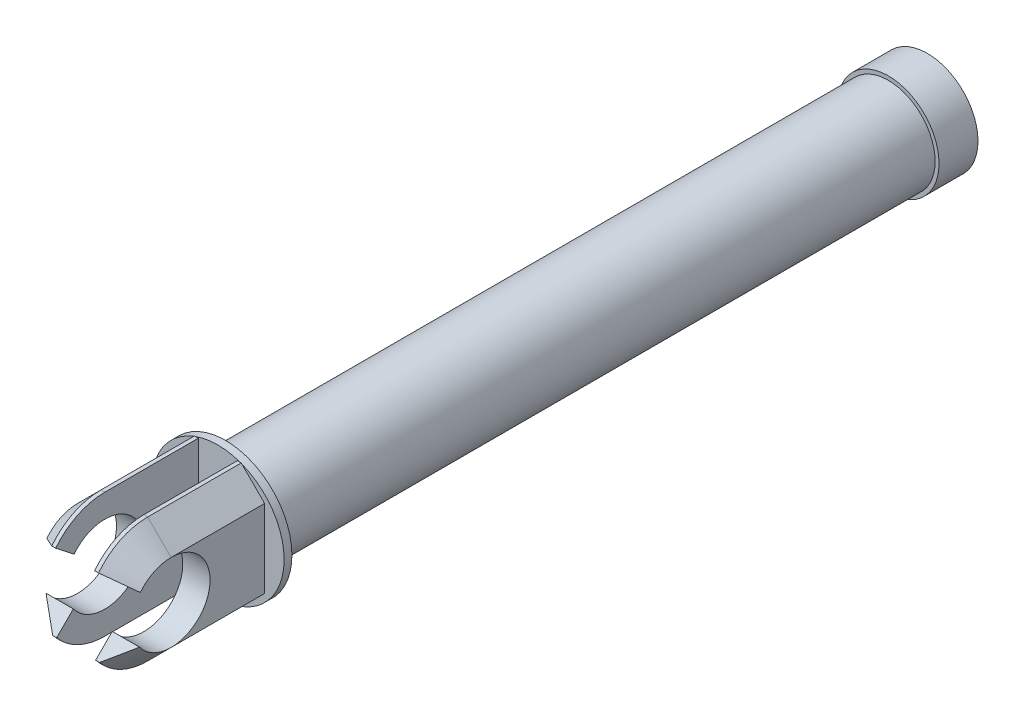
SolidWorks part; units mm, degrees
ref_plane "Front Plane" through (0, 0, 0) normal (0, 0, 1) x (1, 0, 0)
ref_plane "Top Plane" through (0, 0, 0) normal (0, 1, 0) x (1, 0, 0)
ref_plane "Right Plane" through (0, 0, 0) normal (1, 0, 0) x (0, 0, -1)
sketch "Sketch1" plane through (0, 0, 0) normal (0, 0, 1) x (1, 0, 0)
  circle A0 centre (0, 0) radius 12
  circle A1 centre (0, 0) radius 13
  dimension "D1" = 24
  dimension "D2" = 26
extrude "Boss-Extrude1" add sketch "Sketch1" along normal blind 10 contours A0 | A1 A0 | A0 | A1 region at (0, 0, 0) region at (-12.6323, 0, 0)
sketch "Sketch2" plane through (0, 0, 10) normal (0, 0, 1) x (1, 0, 0)
  circle A0 centre (0, 0) radius 12
  dimension "D1" = 24
extrude "Boss-Extrude2" add sketch "Sketch2" along normal blind 170
sketch "Sketch3" plane through (0, 0, 180) normal (0, 0, 1) x (1, 0, 0)
  circle A0 centre (0, 0) radius 17
  dimension "D1" = 34
extrude "Boss-Extrude3" add sketch "Sketch3" along normal blind 2
sketch "Sketch4" plane through (0, 0, 0) normal (1, 0, 0) x (0, 0, -1)
  line L0 (-182, 16) -> (-206, 16)
  line L1 (-182, 17) -> (-182, -17) construction
  line L2 (-206, -16) -> (-182, -16)
  line L3 (-182, -16) -> (-182, 16)
  arc A0 (-206, 16) -> (-206, -16) centre (-206, 0) ccw
  circle A1 centre (-206, 0) radius 10
  point P7 (-182, 0)
  dimension "D2" = 16
  dimension "D3" = 20
  dimension "D1" = 24
extrude "Boss-Extrude4" add sketch "Sketch4" along normal mid plane 24
chamfer "Chamfer1" distance 6 angle 45 6 edges at (-12, -16, 194) (-12, 0, 222) (-12, 16, 194) (12, -16, 194) (12, 0, 222) (12, 16, 194)
sketch "Sketch5" plane through (0, 0, 0) normal (0, 1, 0) x (1, 0, 0)
  line L0 (-5.7446, -182) -> (5.7446, -182) construction
  line L1 (-6, -222) -> (6, -222) construction
  line L2 (6, -206) -> (6, -182) construction
  line L3 (6, -222) -> (6, -206) construction
  line L4 (-6, -206) -> (-6, -222) construction
  line L5 (-6, -182) -> (-6, -206) construction
  line L6 (-5.7446, -182) -> (5.7446, -182)
  line L7 (-6, -222) -> (6, -222)
  line L8 (6, -206) -> (6, -182)
  line L9 (6, -222) -> (6, -206)
  line L10 (-6, -206) -> (-6, -222)
  line L11 (-6, -182) -> (-6, -206)
  line L13 (-5, -182) -> (5, -182)
  line L14 (-5, -182) -> (-5, -223)
  line L15 (-5, -223) -> (5, -223)
  line L16 (5, -182) -> (5, -223)
  dimension "D1" = 1
  dimension "D2" = 1
  dimension "D3" = 1
extrude "Cut-Extrude1" cut sketch "Sketch5" against normal mid plane 40 contours L14 L15 L16 L13
sketch "Sketch6" plane through (12, 0, 0) normal (1, 0, 0) x (0, 0, -1)
  line L0 (-218.6058, 9.8536) -> (-213.8786, 6.1585)
  line L1 (-214.0834, -5.8872) -> (-218.3584, -10.1622)
  line L2 (-206, 10) -> (-206, 16)
  line L3 (-206, -16) -> (-206, -10)
  arc A2 (-206, 16) -> (-206, -16) centre (-206, 0) ccw
  arc A3 (-206, 10) -> (-206, -10) centre (-206, 0) ccw
  arc A4 (-218.6058, 9.8536) -> (-218.3584, -10.1622) centre (-206, 0) ccw
  arc A5 (-213.8786, 6.1585) -> (-214.0834, -5.8872) centre (-206, 0) ccw
  dimension "D1" = 0
extrude "Cut-Extrude2" cut sketch "Sketch6" against normal up to surface (24 mm away) up to face at (-12, 0, 191.5)
